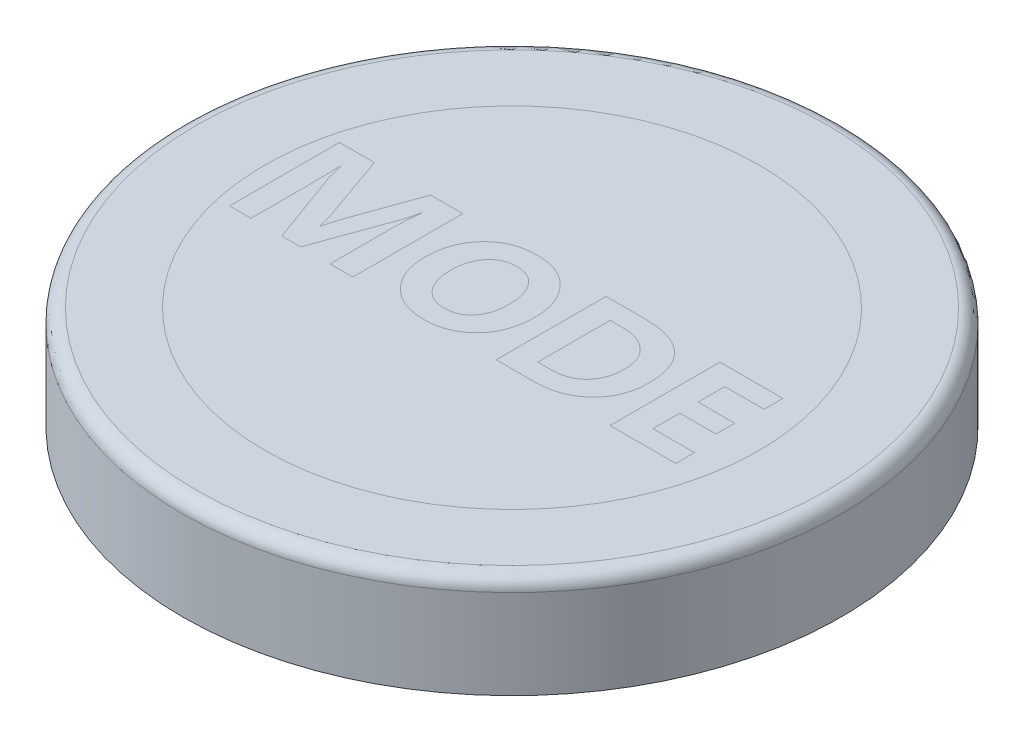
SolidWorks part; units mm, degrees
ref_plane "Front Plane" through (0, 0, 0) normal (0, 0, 1) x (1, 0, 0)
ref_plane "Top Plane" through (0, 0, 0) normal (0, 1, 0) x (1, 0, 0)
ref_plane "Right Plane" through (0, 0, 0) normal (1, 0, 0) x (0, 0, -1)
sketch "Sketch1" plane through (0, 0, 0) normal (0, 1, 0) x (1, 0, 0)
  circle A0 centre (0, 0) radius 4.1
  circle A1 centre (0, 0) radius 3.6
  circle A2 centre (0, 0) radius 4.8
  circle A3 centre (0, 0) radius 4.4
  dimension "D1" = 8.2
  dimension "D2" = 7.2
  dimension "D3" = 9.6
  dimension "D4" = 0.3
extrude "Boss-Extrude1" add sketch "Sketch1" along normal blind 1.5 contours A2 A3 | A1 | A3 A0 region at (0, 0, 0) region at (-4.6642, 0, 0) region at (-4.2755, 0, 0)
extrude "Boss-Extrude3" add sketch "Sketch1<4>" against normal blind 0.1 from surface contours A0 A1 region at (-3.984, 0, 0) starting at face at (0, 1.5, 4.8)
sketch "Sketch1<4>" plane through (0, 0, 0) normal (0, 1, 0) x (1, 0, 0) same geometry as "Sketch1"
fillet "Fillet1" radius 0.2 1 edges at (0, 1.5, 4.8)
sketch "Sketch2" plane through (0, 1.5, 0) normal (0, 1, 0) x (1, 0, 0)
  line L0 (-3.5163, -0.7719) -> (3.5163, -0.7719) construction
  circle A0 centre (0, 0) radius 3.6 construction
  circle A1 centre (0, 0) radius 3.6 construction
  text T0 "MODE" font "Microsoft YaHei" height 1.6
split line "Split Line1"
